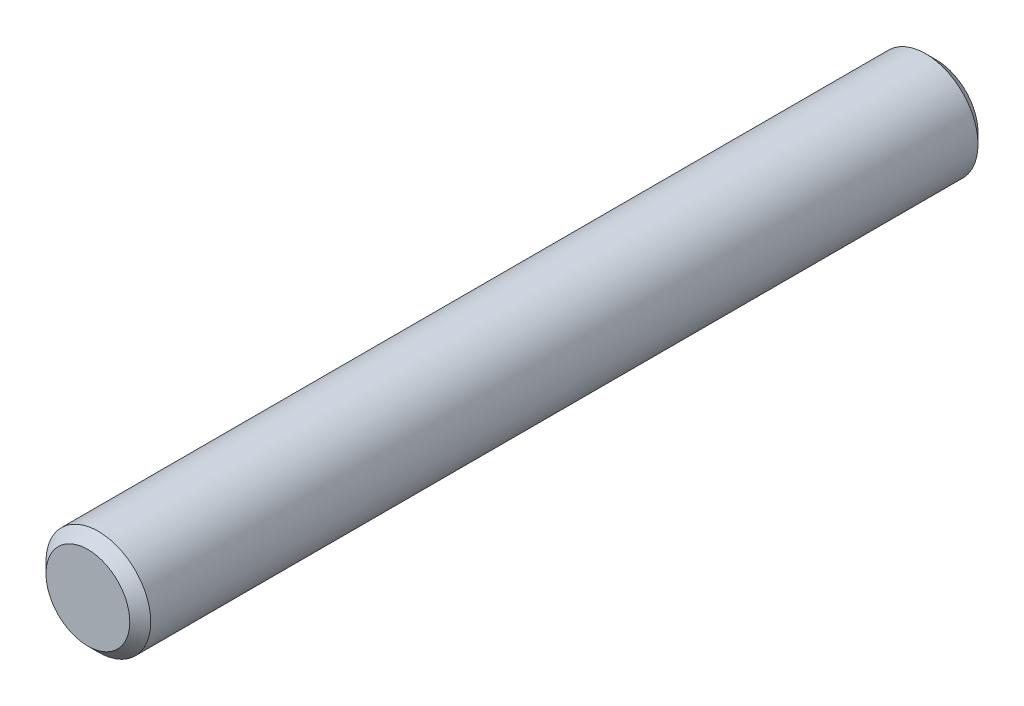
SolidWorks part; units mm, degrees
material "Plain Carbon Steel"
ref_plane "Front" through (0, 0, 0) normal (0, 0, 1) x (1, 0, 0)
ref_plane "Top" through (0, 0, 0) normal (0, 1, 0) x (1, 0, 0)
ref_plane "Right" through (0, 0, 0) normal (1, 0, 0) x (0, 0, -1)
sketch "Sketch1" plane through (0, 0, 0) normal (0, 0, 1) x (1, 0, 0)
  circle A0 centre (0, 0) radius 6.35
  dimension "dia" = 12.7
extrude "Extrude1" add sketch "Sketch1" along normal mid plane 102.87
sketch "Sketch2" plane through (0, 0, 0) normal (1, 0, 0) x (0, 0, -1)
  line L0 (51.435, 6.35) -> (48.895, 6.35) construction
  line L1 (51.435, 6.35) -> (-51.435, 6.35) construction
  line L2 (48.895, 6.35) -> (42.545, 6.35) construction
  line L3 (42.545, 6.35) -> (33.655, 6.35) construction
  line L4 (33.655, 6.35) -> (27.305, 6.35) construction
  line L8 (38.1, 6.35) -> (38.1, -6.35) construction
  line L9 (-51.435, -6.35) -> (51.435, -6.35) construction
  line L10 (27.305, 6.35) -> (18.415, 6.35) construction
  line L11 (18.415, 6.35) -> (12.065, 6.35) construction
  line L12 (12.065, 6.35) -> (3.175, 6.35) construction
  line L13 (3.175, 6.35) -> (-3.175, 6.35) construction
  line L14 (-3.175, 6.35) -> (-12.065, 6.35) construction
  line L15 (26.035, 6.35) -> (26.035, -6.35) construction
  line L16 (10.795, 6.35) -> (10.795, -6.35) construction
  line L17 (-4.445, 6.35) -> (-4.445, -6.35) construction
  line L18 (-12.065, 6.35) -> (-18.415, 6.35) construction
  line L19 (35.6362, 6.35) -> (40.5638, 6.35) construction
  line L20 (35.6362, 6.35) -> (35.6362, -6.35) construction
  line L21 (35.6362, -6.35) -> (40.5638, -6.35) construction
  line L22 (40.5638, 6.35) -> (40.5638, -6.35) construction
  line L23 (-18.415, 6.35) -> (-27.305, 6.35) construction
  line L24 (-27.305, 6.35) -> (-33.655, 6.35) construction
  line L25 (-33.655, 6.35) -> (-42.545, 6.35) construction
  line L26 (-42.545, 6.35) -> (-48.895, 6.35) construction
  line L27 (-19.685, 6.35) -> (-19.685, -6.35) construction
  line L28 (-34.925, 6.35) -> (-34.925, -6.35) construction
  point P0 (-51.435, 6.35)
  point P1 (51.435, 6.35)
  point P30 (38.1, 6.35)
  dimension "D1" = 2.54
  dimension "D2" = 6.35
  dimension "D3" = 8.89
  dimension "D4" = 6.35
  dimension "D5" = 8.89
  dimension "D6" = 6.35
  dimension "D7" = 8.89
  dimension "D8" = 6.35
  dimension "D9" = 8.89
  dimension "D10" = 4.9276
  dimension "D11" = 1.27
  dimension "D12" = 1.27
  dimension "D13" = 1.27
  dimension "D14" = 6.35
  dimension "D15" = 6.35
  dimension "D16" = 8.89
  dimension "D17" = 8.89
  dimension "D18" = 6.35
  dimension "D19" = 1.27
  dimension "D20" = 1.27
chamfer "Chamfer1" distance 1.27 angle 45 2 edges at (6.35, 0, -51.435) (6.35, 0, 51.435)
equation "\"D1@Chamfer1\" = \"dia@Sketch1\" * .1"
